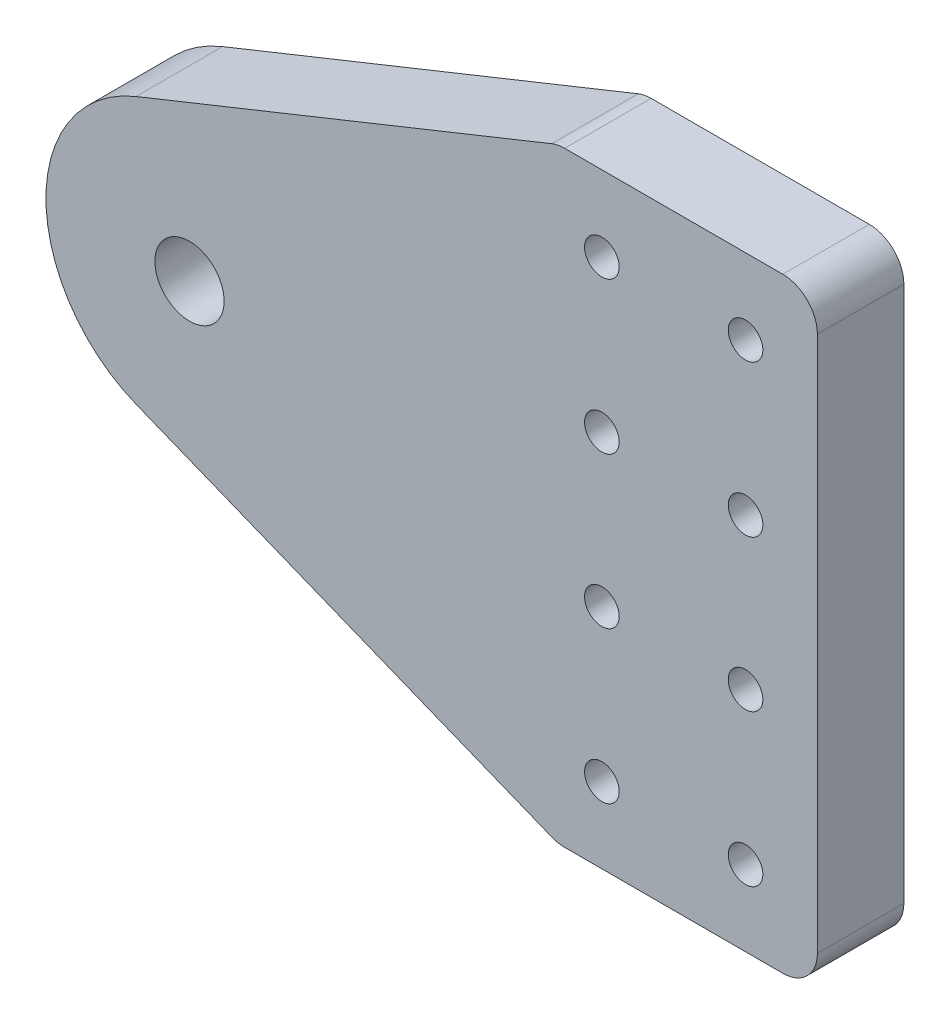
SolidWorks part; units mm, degrees
ref_plane "Front Plane" through (0, 0, 0) normal (0, 0, 1) x (1, 0, 0)
ref_plane "Top Plane" through (0, 0, 0) normal (0, 1, 0) x (1, 0, 0)
ref_plane "Right Plane" through (0, 0, 0) normal (1, 0, 0) x (0, 0, -1)
sketch "Sketch1" plane through (0, 0, 0) normal (0, 0, 1) x (1, 0, 0)
  line L0 (877.2821, -292.1) -> (909.32, -292.1)
  line L1 (914.4, -287.02) -> (914.4, -208.28)
  line L2 (914.4, -225.3961) -> (893.301, -203.2) construction
  line L3 (893.301, -203.2) -> (893.301, -50203.2) construction
  line L4 (876.3, -292.1) -> (876.3, 0) construction
  line L5 (875.3887, -291.7339) -> (814.3403, -267.2129)
  line L6 (838.2, -247.1633) -> (838.2, -50247.1633) construction
  line L7 (821.055, -247.65) -> (50821.055, -247.65) construction
  line L8 (877.2821, -203.2) -> (909.32, -203.2)
  line L9 (875.3887, -203.5661) -> (814.3403, -228.0871)
  line L10 (914.4, -225.425) -> (-49085.6, -225.425) construction
  line L11 (914.4, -269.875) -> (-49085.6, -269.875) construction
  line L12 (893.301, -203.2) -> (893.301, -225.425) construction
  line L13 (893.301, -225.425) -> (914.4, -203.2) construction
  circle A0 centre (822.198, -247.65) radius 16.002 construction
  arc A1 (814.3403, -228.0871) -> (814.3403, -267.2129) centre (822.198, -247.65) ccw
  circle A2 centre (903.8505, -214.298) radius 2.54
  circle A3 centre (882.7516, -214.298) radius 2.54
  circle A4 centre (882.7516, -236.552) radius 2.54
  circle A5 centre (903.8505, -236.552) radius 2.54
  circle A6 centre (882.7516, -258.748) radius 2.54
  circle A7 centre (882.7516, -281.002) radius 2.54
  circle A8 centre (903.8505, -258.748) radius 2.54
  circle A9 centre (903.8505, -281.002) radius 2.54
  arc A10 (877.2821, -203.2) -> (875.3887, -203.5661) centre (877.2821, -208.28) ccw
  arc A11 (877.2821, -292.1) -> (875.3887, -291.7339) centre (877.2821, -287.02) cw
  arc A12 (909.32, -292.1) -> (914.4, -287.02) centre (909.32, -287.02) ccw
  arc A13 (909.32, -203.2) -> (914.4, -208.28) centre (909.32, -208.28) cw
  circle A14 centre (822.198, -247.65) radius 5.08
  point P13 (893.301, -203.2)
  point P31 (903.8505, -214.298)
  point P46 (876.3, -203.2)
  point P49 (876.3, -292.1)
  point P52 (914.4, -292.1)
  dimension "D1" = 32.004
  dimension "D2" = 5.08
  dimension "D5" = 5.08
  dimension "D6" = 5.08
  dimension "D3" = 38.1
  dimension "D4" = 44.45
  dimension "D8" = 22.225
extrude "Boss-Extrude1" add sketch "Sketch1" along normal blind 12.7
